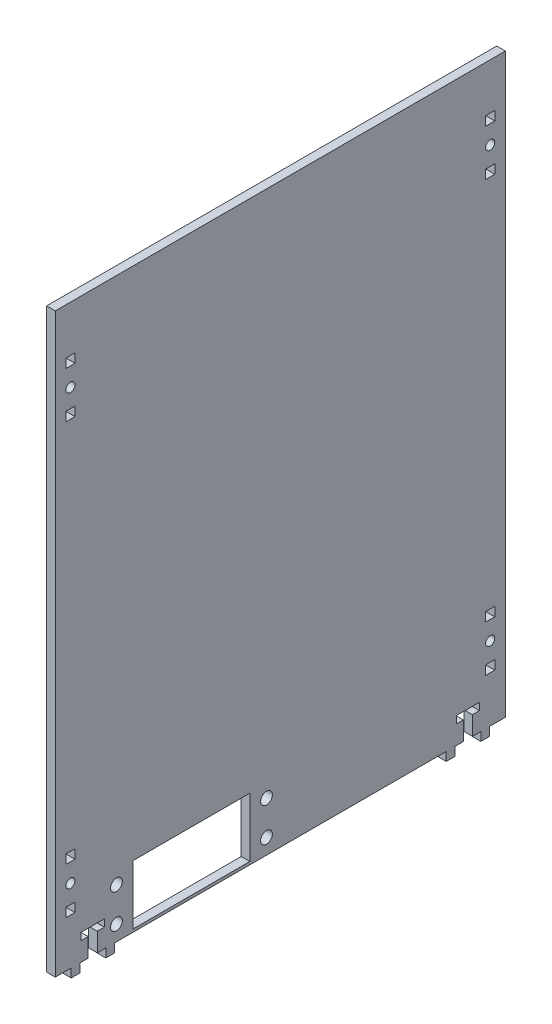
SolidWorks part; units mm, degrees
ref_plane "Front Plane" through (0, 0, 0) normal (0, 0, 1) x (1, 0, 0)
ref_plane "Top Plane" through (0, 0, 0) normal (0, 1, 0) x (1, 0, 0)
ref_plane "Right Plane" through (0, 0, 0) normal (1, 0, 0) x (0, 0, -1)
sketch "Sketch1" plane through (0, 0, 0) normal (1, 0, 0) x (0, 0, -1)
  line L0 (11.425, 0) -> (8.5, 0)
  line L1 (135.5, -3) -> (135.5, 0)
  line L2 (67.45, 21.5) -> (26.95, 21.5)
  line L3 (26.95, 21.5) -> (26.95, 1)
  line L4 (67.45, 21.5) -> (67.45, 1)
  line L5 (26.95, 1) -> (67.45, 1)
  line L6 (8.5, 0) -> (8.5, -3)
  line L7 (8.5, -3) -> (5.5, -3)
  line L8 (0, 0) -> (0, 200)
  line L9 (5.5, -3) -> (5.5, 0)
  line L10 (11.425, 0) -> (11.425, 6.5)
  line L11 (11.425, 6.5) -> (9, 6.5)
  line L12 (9, 6.5) -> (9, 9)
  line L13 (9, 9) -> (17, 9)
  line L14 (17, 9) -> (17, 6.5)
  line L15 (17, 6.5) -> (14.575, 6.5)
  line L16 (14.575, 6.5) -> (14.575, 0)
  line L17 (-1000, 100) -> (49000, 100) construction
  line L18 (3.675, 16) -> (6.825, 16)
  line L19 (3.675, 16) -> (3.675, 19.15)
  line L20 (3.675, 19.15) -> (6.825, 19.15)
  line L21 (6.825, 16) -> (6.825, 19.15)
  line L22 (3.675, 16) -> (6.825, 19.15) construction
  line L23 (3.675, 19.15) -> (6.825, 16) construction
  line L24 (3.675, 32) -> (6.825, 32)
  line L25 (3.675, 32) -> (3.675, 35.15)
  line L26 (3.675, 35.15) -> (6.825, 35.15)
  line L27 (6.825, 32) -> (6.825, 35.15)
  line L28 (3.675, 32) -> (6.825, 35.15) construction
  line L29 (3.675, 35.15) -> (6.825, 32) construction
  line L30 (14.575, 0) -> (17.5, 0)
  line L31 (78, -1000) -> (78, 49000) construction
  line L32 (3.675, 164.85) -> (6.825, 168) construction
  line L33 (3.675, 168) -> (6.825, 164.85) construction
  line L34 (3.675, 180.85) -> (6.825, 184) construction
  line L35 (3.675, 184) -> (6.825, 180.85) construction
  line L36 (0, 200) -> (156, 200)
  line L37 (6.825, 168) -> (6.825, 164.85)
  line L38 (3.675, 164.85) -> (6.825, 164.85)
  line L39 (3.675, 168) -> (3.675, 164.85)
  line L40 (3.675, 168) -> (6.825, 168)
  line L41 (6.825, 184) -> (6.825, 180.85)
  line L42 (3.675, 180.85) -> (6.825, 180.85)
  line L43 (3.675, 184) -> (3.675, 180.85)
  line L44 (3.675, 184) -> (6.825, 184)
  line L45 (5.5, 0) -> (0, 0)
  line L46 (17.5, 0) -> (17.5, -3)
  line L47 (17.5, -3) -> (20.5, -3)
  line L48 (20.5, -3) -> (20.5, 0)
  line L49 (20.5, 0) -> (135.5, 0)
  line L50 (138.5, -3) -> (135.5, -3)
  line L51 (138.5, 0) -> (138.5, -3)
  line L52 (141.425, 0) -> (138.5, 0)
  line L53 (144.575, 0) -> (147.5, 0)
  line L54 (150.5, 0) -> (156, 0)
  line L55 (150.5, -3) -> (150.5, 0)
  line L56 (147.5, -3) -> (150.5, -3)
  line L57 (147.5, 0) -> (147.5, -3)
  line L61 (152.325, 184) -> (149.175, 180.85) construction
  line L62 (152.325, 180.85) -> (149.175, 184) construction
  line L63 (152.325, 168) -> (149.175, 164.85) construction
  line L64 (152.325, 164.85) -> (149.175, 168) construction
  line L65 (152.325, 35.15) -> (149.175, 32) construction
  line L66 (152.325, 32) -> (149.175, 35.15) construction
  line L67 (152.325, 19.15) -> (149.175, 16) construction
  line L68 (152.325, 16) -> (149.175, 19.15) construction
  line L85 (152.325, 184) -> (149.175, 184)
  line L86 (152.325, 184) -> (152.325, 180.85)
  line L87 (152.325, 180.85) -> (149.175, 180.85)
  line L88 (149.175, 184) -> (149.175, 180.85)
  line L89 (152.325, 168) -> (149.175, 168)
  line L90 (152.325, 168) -> (152.325, 164.85)
  line L91 (152.325, 164.85) -> (149.175, 164.85)
  line L92 (149.175, 168) -> (149.175, 164.85)
  line L93 (149.175, 32) -> (149.175, 35.15)
  line L94 (152.325, 35.15) -> (149.175, 35.15)
  line L95 (152.325, 32) -> (152.325, 35.15)
  line L96 (152.325, 32) -> (149.175, 32)
  line L97 (149.175, 16) -> (149.175, 19.15)
  line L98 (152.325, 19.15) -> (149.175, 19.15)
  line L99 (152.325, 16) -> (152.325, 19.15)
  line L100 (152.325, 16) -> (149.175, 16)
  line L101 (141.425, 6.5) -> (141.425, 0)
  line L102 (139, 6.5) -> (141.425, 6.5)
  line L103 (139, 9) -> (139, 6.5)
  line L104 (147, 9) -> (139, 9)
  line L105 (147, 6.5) -> (147, 9)
  line L106 (144.575, 6.5) -> (147, 6.5)
  line L107 (144.575, 0) -> (144.575, 6.5)
  line L109 (156, 0) -> (156, 200)
  circle A0 centre (5.25, 25.575) radius 1.575
  circle A1 centre (5.25, 174.425) radius 1.575
  circle A2 centre (150.75, 174.425) radius 1.575
  circle A3 centre (150.75, 25.575) radius 1.575
  circle A4 centre (73.2, 5.35) radius 2.05
  circle A5 centre (73.2, 17.15) radius 2.05
  circle A6 centre (21.2, 5.35) radius 2.05
  circle A7 centre (21.2, 17.15) radius 2.05
  point P3 (13, 9)
  point P4 (143, 9)
  point P16 (5.25, 17.575)
  point P29 (5.25, 33.575)
  point P58 (0, 100)
  point P63 (0, 0)
  point P65 (5.25, 166.425)
  point P66 (5.25, 182.425)
  point P88 (78, 0)
  point P104 (78, 200)
  point P105 (78, 0)
  point P121 (150.75, 182.425)
  point P122 (150.75, 166.425)
  point P123 (156, 100)
  point P124 (150.75, 33.575)
  point P125 (150.75, 17.575)
  dimension "D19" = 3.15
  dimension "D23" = 20.5
  dimension "D24" = 4.1
  dimension "D25" = 4.1
  dimension "D30" = 4.1
  dimension "D31" = 4.1
  dimension "D3" = 130
  dimension "D4" = 156
  dimension "D5" = 5.25
  dimension "D6" = 4.5
  dimension "D7" = 4.5
  dimension "D8" = 2.5
  dimension "D9" = 100
  dimension "D10" = 2.5
  dimension "D11" = 8
  dimension "D12" = 8
  dimension "D13" = 8
  dimension "D14" = 3.15
  dimension "D15" = 2.425
  dimension "D16" = 3.15
  dimension "D17" = 3.15
  dimension "D18" = 5.75
  dimension "D20" = 5.75
  dimension "D21" = 3.15
  dimension "D22" = 3.15
  dimension "D26" = 4.35
  dimension "D27" = 4.35
  dimension "D28" = 3
  dimension "D29" = 5.75
  dimension "D32" = 5.75
  dimension "D33" = 4.35
  dimension "D34" = 4.35
  dimension "D35" = 9.95
  dimension "D36" = 40.5
  dimension "D37" = 11.8
  dimension "D38" = 3
  dimension "D39" = 3
  dimension "D40" = 3
  dimension "D41" = 9
  dimension "D42" = 17.575
  dimension "D43" = 1
extrude "Boss-Extrude2" add sketch "Sketch1" along normal blind 1.5 and the other way blind 1.5
